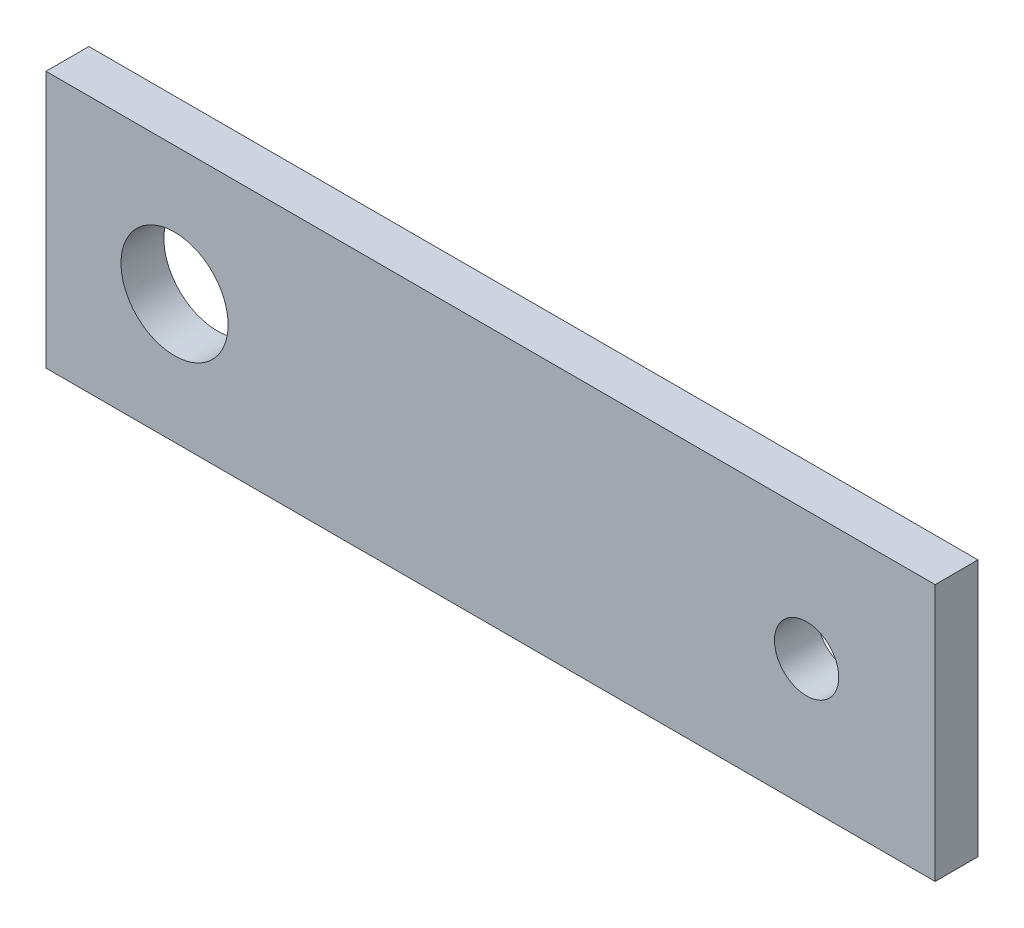
SolidWorks part; units mm, degrees
ref_plane "前视基准面" through (0, 0, 0) normal (0, 0, 1) x (1, 0, 0)
ref_plane "上视基准面" through (0, 0, 0) normal (0, 1, 0) x (1, 0, 0)
ref_plane "右视基准面" through (0, 0, 0) normal (1, 0, 0) x (0, 0, -1)
other "Configuration Table"
sketch "草图1" plane through (0, 0, 0) normal (0, 0, 1) x (1, 0, 0)
  line L1 (-12, -12) -> (71, -12)
  line L2 (-12, -12) -> (-12, 12)
  line L3 (-12, 12) -> (71, 12)
  line L4 (71, -12) -> (71, 12)
  line L5 (-12, -12) -> (71, 12) construction
  line L6 (-12, 12) -> (71, -12) construction
  circle A0 centre (0, 0) radius 5
  circle A1 centre (59, 0) radius 3
  point P0 (29.5, 0)
extrude "凸台-拉伸1" add sketch "草图1" along normal mid plane 4
